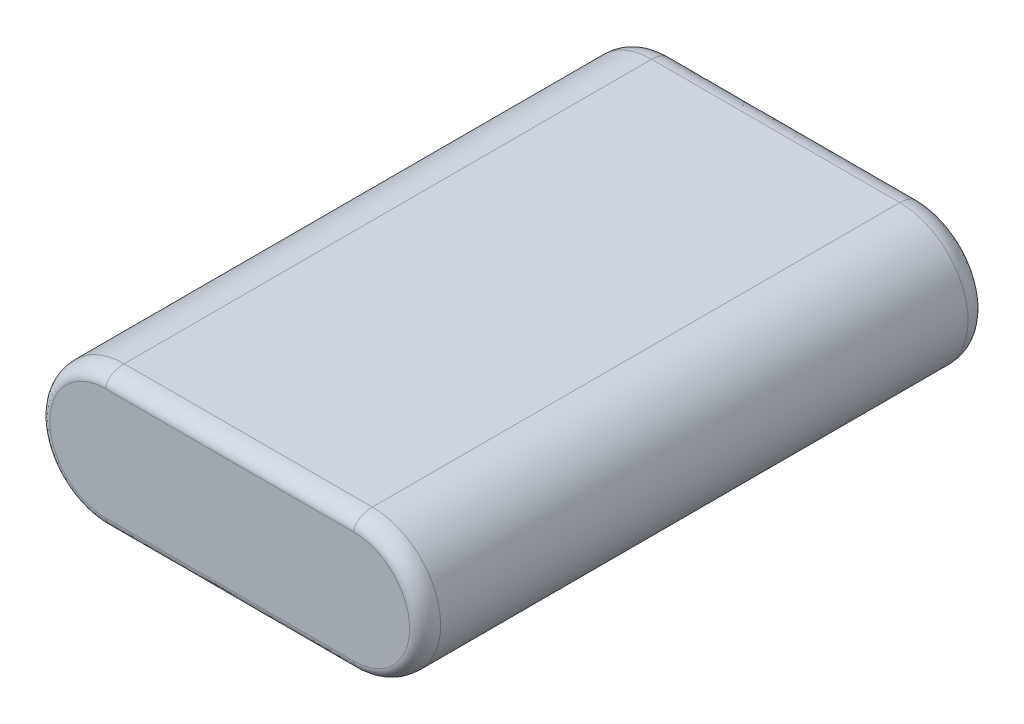
SolidWorks part; units mm, degrees
ref_plane "正面" through (0, 0, 0) normal (0, 0, 1) x (1, 0, 0)
ref_plane "平面" through (0, 0, 0) normal (0, 1, 0) x (1, 0, 0)
ref_plane "右側面" through (0, 0, 0) normal (1, 0, 0) x (0, 0, -1)
sketch "ｽｹｯﾁ1" plane through (0, 0, 0) normal (0, 0, 1) x (1, 0, 0)
  line L0 (20, 0) -> (-20, 0) construction
  line L1 (20, -11) -> (-20, -11)
  line L2 (20, 11) -> (-20, 11)
  arc A0 (20, -11) -> (20, 11) centre (20, 0) ccw
  arc A1 (-20, 11) -> (-20, -11) centre (-20, 0) ccw
  point P2 (0, 0)
  dimension "D1" = 11
  dimension "D2" = 40
extrude "ﾎﾞｽ - 押し出し1" add sketch "ｽｹｯﾁ1" along normal blind 91
fillet "ﾌｨﾚｯﾄ1" radius 3 4 edges at (0, -11, 91) (31, 0, 91) (-31, 0, 91) (0, 11, 91) second distance 2 first distance on face at (0, -11, 45.5) first distance on face at (25.5, 0, 45.5) first distance on face at (-25.5, 0, 45.5) first distance on face at (0, 11, 45.5)
fillet "ﾌｨﾚｯﾄ2" radius 2 4 edges at (-31, 0, 0) (0, -11, 0) (0, 11, 0) (31, 0, 0) second distance 3 first distance on face at (0, 0, 0)
